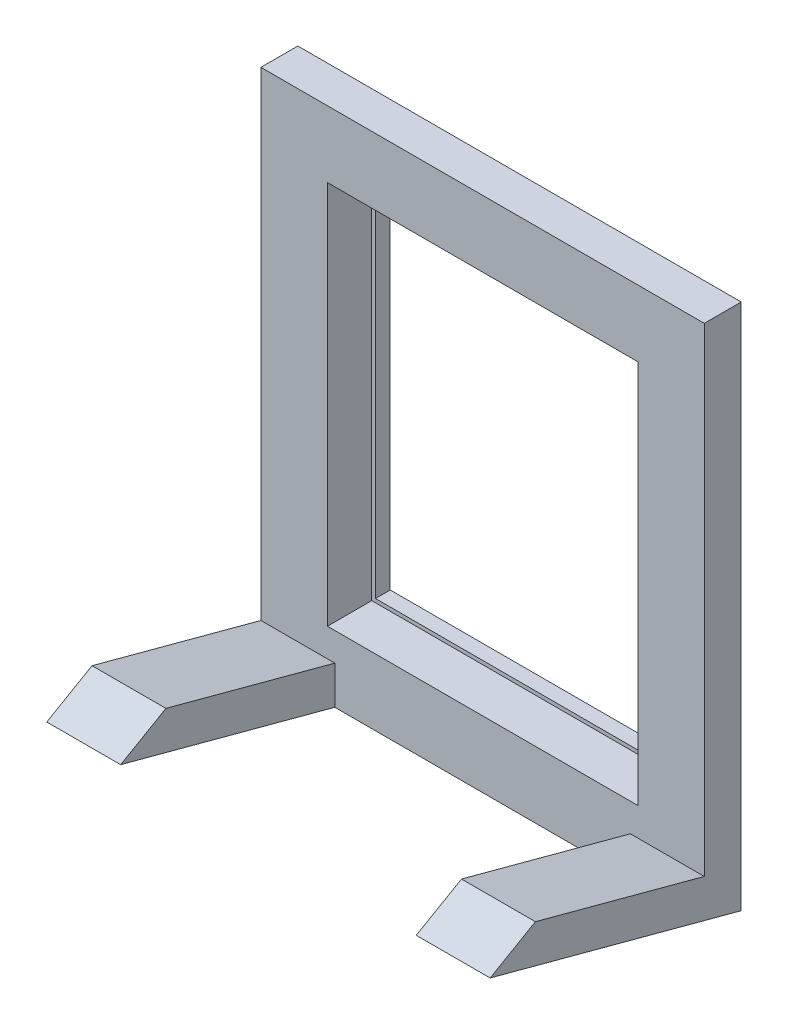
SolidWorks part; units mm, degrees
material "ABS"
ref_plane "Спереди" through (0, 0, 0) normal (0, 0, 1) x (1, 0, 0)
ref_plane "Сверху" through (0, 0, 0) normal (0, 1, 0) x (1, 0, 0)
ref_plane "Справа" through (0, 0, 0) normal (1, 0, 0) x (0, 0, -1)
sketch "Эскиз1" plane through (0, 0, 0) normal (0, 0, 1) x (1, 0, 0)
  line L5 (-30, -35) -> (30, -35)
  line L6 (-30, -35) -> (-30, 35)
  line L7 (-30, 35) -> (30, 35)
  line L8 (30, -35) -> (30, 35)
  line L9 (-30, -35) -> (30, 35) construction
  line L10 (-30, 35) -> (30, -35) construction
  line L11 (-20.5, -25.5) -> (20.5, -25.5)
  line L12 (-20.5, -25.5) -> (-20.5, 25.5)
  line L13 (-20.5, 25.5) -> (20.5, 25.5)
  line L14 (20.5, -25.5) -> (20.5, 25.5)
  line L15 (-20.5, -25.5) -> (20.5, 25.5) construction
  line L16 (-20.5, 25.5) -> (20.5, -25.5) construction
  point P0 (0, 0)
  point P5 (0, 0)
  dimension "D1" = 41
  dimension "D2" = 51
  dimension "D3" = 70
  dimension "D4" = 60
extrude "Бобышка-Вытянуть1" add sketch "Эскиз1" along normal blind 6 and the other way blind 2
sketch "Эскиз2" plane through (0, 0, 0) normal (0, 0, -1) x (-1, 0, 0)
  line L1 (-21, 26) -> (21, 26)
  line L2 (-21, 26) -> (-21, -26)
  line L3 (-21, -26) -> (21, -26)
  line L4 (21, 26) -> (21, -26)
  line L5 (-21, 26) -> (21, -26) construction
  line L6 (-21, -26) -> (21, 26) construction
  point P0 (0, 0)
  dimension "D1" = 52
  dimension "D2" = 42
extrude "Вырез-Вытянуть2" cut sketch "Эскиз2" against normal through all
sketch "Эскиз3" plane through (0, -35, 0) normal (0, -1, 0) x (-1, 0, 0)
  line L1 (-30, 2) -> (-26, 2)
  line L2 (-30, 2) -> (-30, -1)
  line L3 (-30, -1) -> (-26, -1)
  line L4 (-26, 2) -> (-26, -1)
  dimension "D1" = 4
  dimension "D2" = 3
sketch "Эскиз4" plane through (0, 0, -2) normal (0, 0, -1) x (-1, 0, 0)
  line L4 (-30, 35) -> (-30, -35)
  line L6 (-30, 35) -> (-30, -35)
  line L12 (-30, -35) -> (30, -35)
  line L14 (-30, -35) -> (30, -35)
  line L16 (30, -35) -> (30, 35)
  line L17 (30, -35) -> (30, 35)
  line L18 (30, 35) -> (-30, 35)
  line L19 (30, 35) -> (-30, 35)
  dimension "D1" = 0
sweep "Вырез-По траектории1" cut profiles "Эскиз3" path "Эскиз4"
chamfer "Фаска2" distance 3 angle 45 4 edges at (26, 0, -2) (0, 31, -2) (-26, 0, -2) (0, -31, -2)
sketch "Эскиз5" plane through (30, 0, 0) normal (1, 0, 0) x (0, 0, -1)
  line L0 (-6, -35) -> (-21.8653, -35) construction
  line L1 (-6, -35) -> (-34.9778, -27.2354)
  line L2 (-34.9778, -27.2354) -> (-28.8541, -23.6999)
  line L3 (-28.8541, -23.6999) -> (-6, -29.8236)
  line L4 (-6, -35) -> (-6, 35) construction
  line L5 (-6, -29.8236) -> (-6, -35)
  line L9 (-6, -35) -> (-1, -35)
  line L10 (-1, -35) -> (-1, 35)
  line L11 (-1, 35) -> (-6, 35)
  line L12 (-6, 35) -> (-6, -35)
  line L13 (-6, -35) -> (-1, -35)
  line L14 (-1, -35) -> (-1, 35)
  line L15 (-1, 35) -> (-6, 35)
  line M12 (-6, 35) -> (-6, -35)
  dimension "D1" = 15
  dimension "D2" = 5
  dimension "D3" = 45
  dimension "D4" = 30
  dimension "D5" = 0
extrude "Бобышка-Вытянуть2" add sketch "Эскиз5" against normal blind 10 contours L3 L2 L1 M12 region at (30, -29.0255, 19.0182)
mirror "Зеркальное отражение1" about plane through (0, 0, 0) normal (1, 0, 0) of "Бобышка-Вытянуть2"
sketch "Эскиз6" plane through (30, 0, 0) normal (1, 0, 0) x (0, 0, -1)
  line L0 (-6, -35) -> (-1, -36.3397)
  line L1 (-1, -36.3397) -> (-1, -35)
  line L2 (-1, -35) -> (-6, -35)
extrude "Бобышка-Вытянуть3" add sketch "Эскиз6" against normal blind 60
